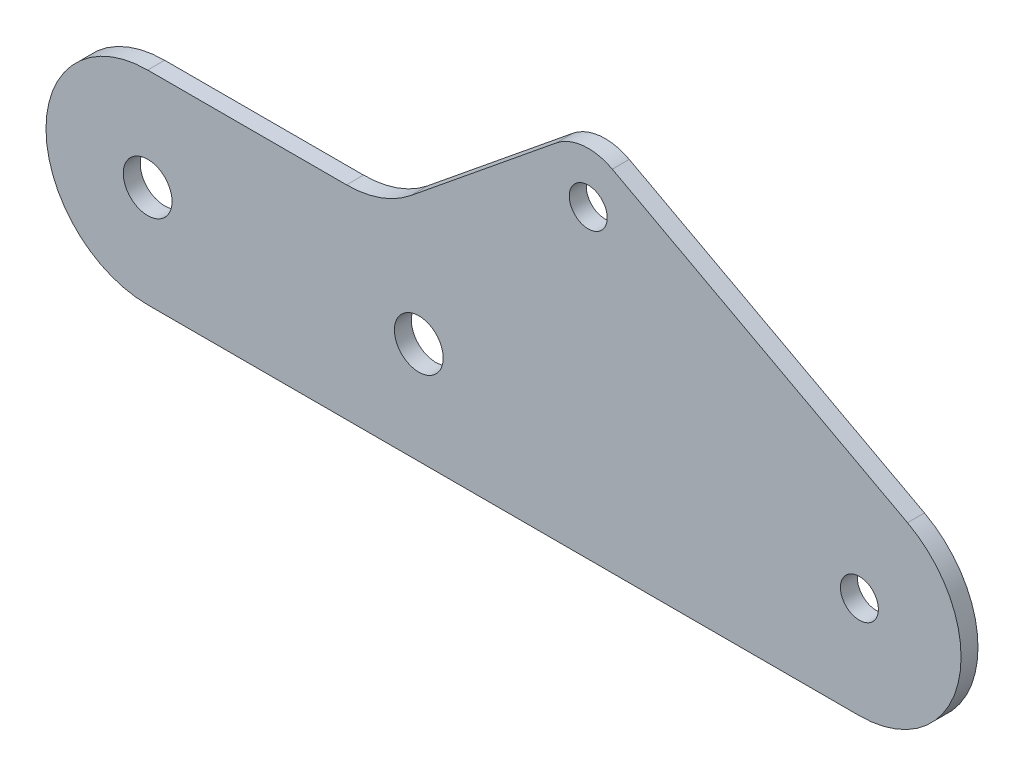
SolidWorks part; units mm, degrees
ref_plane "Front Plane" through (0, 0, 0) normal (0, 0, 1) x (1, 0, 0)
ref_plane "Top Plane" through (0, 0, 0) normal (0, 1, 0) x (1, 0, 0)
ref_plane "Right Plane" through (0, 0, 0) normal (1, 0, 0) x (0, 0, -1)
sketch "Sketch1" plane through (0, 0, 0) normal (0, 0, 1) x (1, 0, 0)
  line L1 (-3.9295, -9.525) -> (41.275, -9.525)
  line L2 (-0.7587, 11.6604) -> (12.87, 22.7448)
  line L3 (45.7823, 8.391) -> (18.1287, 23.2455)
  line L4 (-25.4, 9.525) -> (-6.7687, 9.525)
  line L5 (-25.4, -9.525) -> (-3.9295, -9.525)
  line L6 (-0.7587, 11.6604) -> (-12.5359, 2.082) construction
  circle A1 centre (0, 0) radius 2.286
  circle A2 centre (41.275, 0) radius 1.778
  arc A3 (41.275, -9.525) -> (45.7823, 8.391) centre (41.275, 0) ccw
  arc A4 (18.1287, 23.2455) -> (12.87, 22.7448) centre (15.875, 19.05) ccw
  circle A5 centre (15.875, 19.05) radius 1.778
  circle A6 centre (-25.4, 0) radius 2.286
  arc A7 (-25.4, 9.525) -> (-25.4, -9.525) centre (-25.4, 0) ccw
  arc A8 (-6.7687, 9.525) -> (-0.7587, 11.6604) centre (-6.7687, 19.05) ccw
  point P21 (0, 0)
  point P23 (0, 0)
  point P24 (0, 0)
  point P25 (0, 0)
  point P26 (-3.3665, -2.278)
  dimension "D1" = 9.525
  dimension "D2" = 4.572
  dimension "D4" = 19.05
  dimension "D3" = 9.525
  dimension "D7" = 3.556
  dimension "D8" = 19.05
  dimension "D5" = 25.4
  dimension "D6" = 19.05
  dimension "D9" = 9.525
  dimension "D10" = 25.4
  dimension "D11" = 41.275
extrude "Boss-Extrude1" add sketch "Sketch1" along normal blind 1.5875
